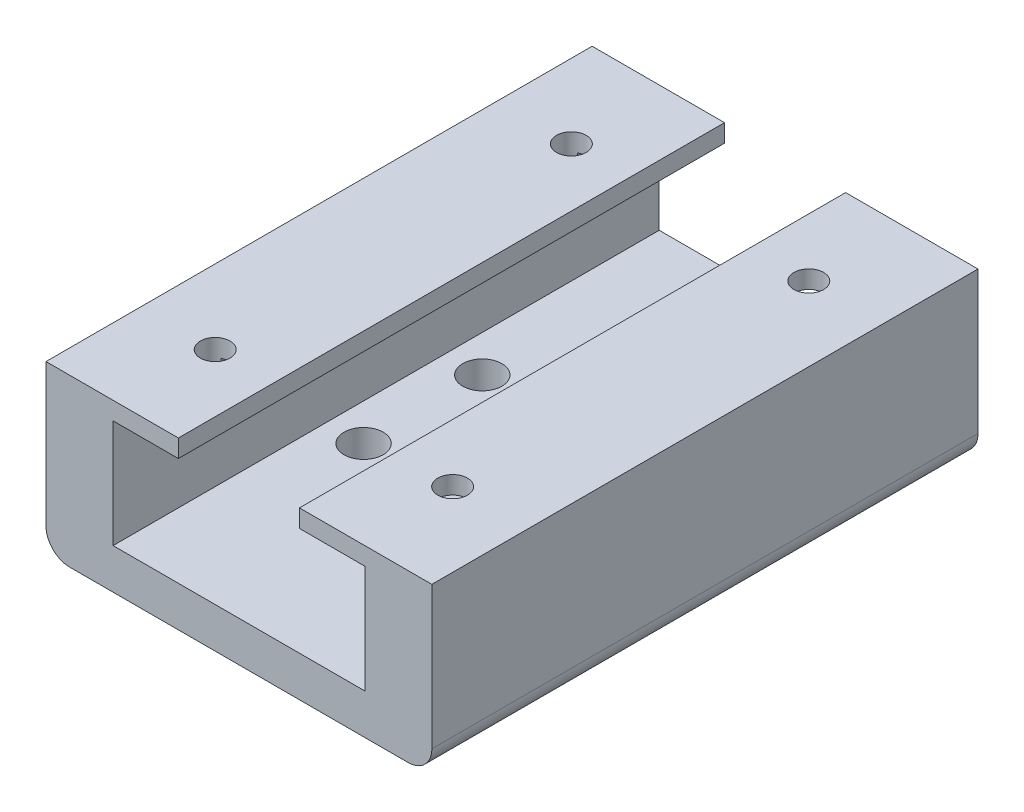
SolidWorks part; units mm, degrees
ref_plane "前视基准面" through (0, 0, 0) normal (0, 0, 1) x (1, 0, 0)
ref_plane "上视基准面" through (0, 0, 0) normal (0, 1, 0) x (1, 0, 0)
ref_plane "右视基准面" through (0, 0, 0) normal (1, 0, 0) x (0, 0, -1)
sketch "草图1" plane through (0, 0, 0) normal (0, 1, 0) x (1, 0, 0)
  line L1 (16.25, -23) -> (-16.25, -23)
  line L2 (16.25, -23) -> (16.25, 23)
  line L3 (16.25, 23) -> (-16.25, 23)
  line L4 (-16.25, -23) -> (-16.25, 23)
  line L5 (16.25, -23) -> (-16.25, 23) construction
  line L6 (16.25, 23) -> (-16.25, -23) construction
  point P0 (0, 0)
  dimension "D1" = 32.5
  dimension "D2" = 46
extrude "凸台-拉伸1" add sketch "草图1" along normal blind 14
sketch "草图2" plane through (0, 0, -23) normal (0, 0, -1) x (-1, 0, 0)
  line L0 (-16.25, 14) -> (16.25, 14) construction
  line L1 (-5.1, 12.5) -> (5.1, 12.5)
  line L2 (-5.1, 12.5) -> (-5.1, 14)
  line L3 (-5.1, 14) -> (5.1, 14)
  line L4 (5.1, 12.5) -> (5.1, 14)
  line L5 (-5.1, 12.5) -> (5.1, 14) construction
  line L6 (-5.1, 14) -> (5.1, 12.5) construction
  line L8 (-10.6, 3.4) -> (10.6, 3.4)
  line L9 (-10.6, 3.4) -> (-10.6, 12.5)
  line L10 (-10.6, 12.5) -> (10.6, 12.5)
  line L11 (10.6, 3.4) -> (10.6, 12.5)
  line L12 (-10.6, 3.4) -> (10.6, 12.5) construction
  line L13 (-10.6, 12.5) -> (10.6, 3.4) construction
  point P0 (0, 13.25)
  point P9 (0, 7.95)
  line M7 (16.25, 14) -> (-16.25, 14)
  dimension "D1" = 1.5
  dimension "D2" = 10.2
  dimension "D3" = 21.2
  dimension "D4" = 10.6
  dimension "D5" = 0
extrude "切除-拉伸2" cut sketch "草图2" against normal through all contours L1 L4 L2 M7 | L8 L11 L10 L1 L9 region at (0, 13.25, -23) region at (0, 7.95, -23)
sketch "草图4" plane through (0, 0, 0) normal (0, -1, 0) x (1, 0, 0)
  line L1 (-7.5, -5) -> (7.5, -5) construction
  line L2 (-7.5, -5) -> (-7.5, 5) construction
  line L3 (-7.5, 5) -> (7.5, 5) construction
  line L4 (7.5, -5) -> (7.5, 5) construction
  line L5 (-7.5, -5) -> (7.5, 5) construction
  line L6 (-7.5, 5) -> (7.5, -5) construction
  circle A0 centre (-7.5, 5) radius 1.65
  circle A1 centre (7.5, 5) radius 1.65
  circle A2 centre (7.5, -5) radius 1.65
  circle A3 centre (-7.5, -5) radius 1.65
  point P0 (0, 0)
  dimension "D3" = 3.3
  dimension "D4" = 3.3
  dimension "D5" = 3.3
  dimension "D6" = 3.3
  dimension "D1" = 15
  dimension "D2" = 10
extrude "切除-拉伸3" cut sketch "草图4" against normal up to next
sketch "草图5" plane through (0, 14, 0) normal (0, 1, 0) x (1, 0, 0)
  line L1 (-10, -15) -> (10, -15) construction
  line L2 (-10, -15) -> (-10, 15) construction
  line L3 (-10, 15) -> (10, 15) construction
  line L4 (10, -15) -> (10, 15) construction
  line L5 (-10, -15) -> (10, 15) construction
  line L6 (-10, 15) -> (10, -15) construction
  circle A0 centre (-10, 15) radius 1.25
  circle A1 centre (10, 15) radius 1.25
  circle A2 centre (10, -15) radius 1.25
  circle A3 centre (-10, -15) radius 1.25
  point P0 (0, 0)
  dimension "D3" = 2.5
  dimension "D4" = 2.5
  dimension "D5" = 2.5
  dimension "D6" = 2.5
  dimension "D1" = 30
  dimension "D2" = 20
extrude "切除-拉伸4" cut sketch "草图5" against normal blind 2
fillet "圆角1" radius 2 2 edges at (16.25, 0, 0) (-16.25, 0, 0)
equation "\"33.5.00mm\"=34"
